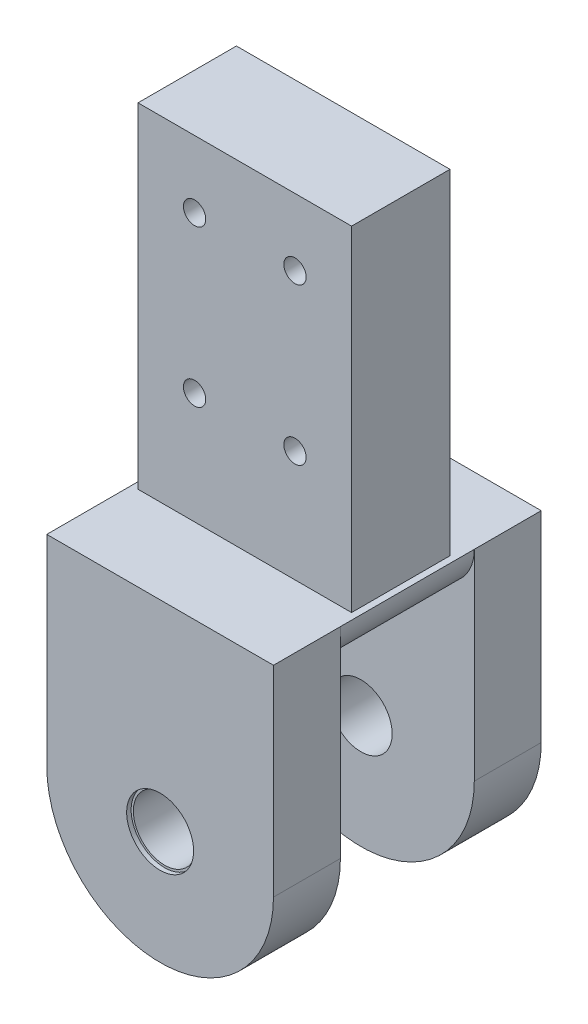
SolidWorks part; units mm, degrees
ref_plane "Front Plane" through (0, 0, 0) normal (0, 0, 1) x (1, 0, 0)
ref_plane "Top Plane" through (0, 0, 0) normal (0, 1, 0) x (1, 0, 0)
ref_plane "Right Plane" through (0, 0, 0) normal (1, 0, 0) x (0, 0, -1)
sketch "Sketch1" plane through (0, 0, 0) normal (0, 0, 1) x (1, 0, 0)
  line L0 (-25.4, 0) -> (-25.4, 120)
  line L1 (-25.4, 120) -> (25.4, 120)
  line L2 (25.4, 120) -> (25.4, 0)
  line L4 (-11.25, 105) -> (11.25, 105) construction
  line L5 (-11.25, 105) -> (-11.25, 70) construction
  line L6 (-11.25, 70) -> (11.25, 70) construction
  line L7 (11.25, 105) -> (11.25, 70) construction
  circle A0 centre (0, 0) radius 7
  arc A1 (-25.4, 0) -> (25.4, 0) centre (0, 0) ccw
  circle A2 centre (-11.25, 105) radius 2.5
  circle A3 centre (11.25, 105) radius 2.5
  circle A4 centre (11.25, 70) radius 2.5
  circle A5 centre (-11.25, 70) radius 2.5
  point P13 (0, 70)
  dimension "D1" = 14
  dimension "D4" = 5
  dimension "D2" = 50.8
  dimension "D3" = 120
  dimension "D5" = 35
  dimension "D6" = 15
  dimension "D7" = 22.5
extrude "Boss-Extrude1" add sketch "Sketch1" along normal mid plane 60
sketch "Sketch2" plane through (25.4, 0, 0) normal (1, 0, 0) x (0, 0, -1)
  line L0 (-30, -25.4) -> (30, -25.4) construction
  line L1 (-15, 35) -> (15, 35)
  line L2 (-15, 35) -> (-15, -25.4)
  line L3 (-15, -25.4) -> (15, -25.4)
  line L4 (15, 35) -> (15, -25.4)
  line L5 (-30, 0) -> (30, 0) construction
  point P8 (0, 0)
  point P9 (0, 35)
  dimension "D1" = 30
  dimension "D2" = 35
extrude "Cut-Extrude1" cut sketch "Sketch2" against normal through all
sketch "Sketch3" plane through (0, 0, 30) normal (0, 0, 1) x (1, 0, 0)
  circle A0 centre (0, 0) radius 7.5
  dimension "D1" = 15
extrude "Cut-Extrude2" cut sketch "Sketch3" against normal blind 1
sketch "Sketch4" plane through (0, 0, -30) normal (0, 0, -1) x (-1, 0, 0)
  circle A0 centre (0, 0) radius 7.5
  dimension "D1" = 15
extrude "Cut-Extrude3" cut sketch "Sketch4" against normal blind 1
sketch "Sketch6" plane through (25.4, 0, 0) normal (1, 0, 0) x (0, 0, -1)
  line L1 (-30, 120) -> (-12.7, 120)
  line L2 (-30, 120) -> (-30, 45)
  line L3 (-30, 45) -> (-12.7, 45)
  line L4 (-12.7, 120) -> (-12.7, 45)
  line L5 (30, 120) -> (12.7, 120)
  line L6 (30, 120) -> (30, 45)
  line L7 (30, 45) -> (12.7, 45)
  line L8 (12.7, 120) -> (12.7, 45)
  dimension "D1" = 25.4
  dimension "D2" = 75
extrude "Cut-Extrude4" cut sketch "Sketch6" against normal through all
sketch "Sketch7" plane through (0, 45, 0) normal (0, 1, 0) x (1, 0, 0)
  line L0 (-25.4, 12.7) -> (-25.4, 30) construction
  line L1 (-23.93, -11.025) -> (23.93, -11.025)
  line L2 (-23.93, -11.025) -> (-23.93, 11.025)
  line L3 (-23.93, 11.025) -> (23.93, 11.025)
  line L4 (23.93, -11.025) -> (23.93, 11.025)
  line L5 (-23.93, -11.025) -> (23.93, 11.025) construction
  line L6 (-23.93, 11.025) -> (23.93, -11.025) construction
  line L7 (25.4, -12.7) -> (-25.4, -12.7)
  line L8 (25.4, -12.7) -> (25.4, 12.7)
  line L9 (25.4, 12.7) -> (-25.4, 12.7)
  line L10 (-25.4, -12.7) -> (-25.4, 12.7)
  line L11 (25.4, -12.7) -> (-25.4, 12.7) construction
  line L12 (25.4, 12.7) -> (-25.4, -12.7) construction
  line L13 (-25.4, 12.7) -> (25.4, 12.7) construction
  point P0 (0, 0)
  point P6 (0, 0)
  dimension "D1" = 47.86
  dimension "D2" = 22.05
extrude "Cut-Extrude5" cut sketch "Sketch7" along normal through all
fillet "Fillet1" radius 10 2 edges at (25.4, 35, 0) (-25.4, 35, 0)
